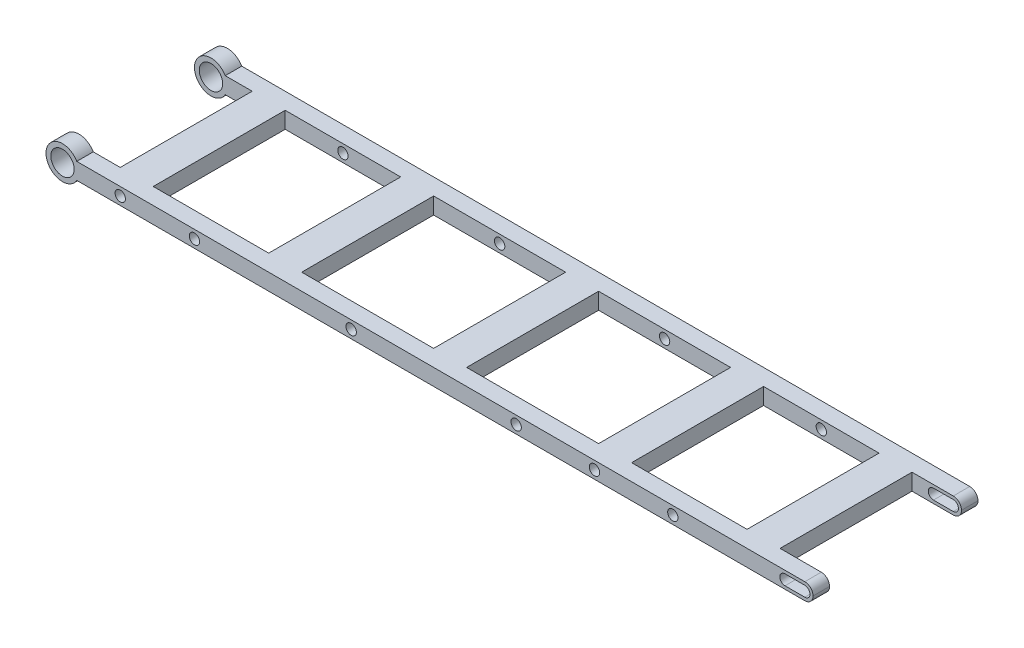
SolidWorks part; units mm, degrees
ref_plane "Front Plane" through (0, 0, 0) normal (0, 0, 1) x (1, 0, 0)
ref_plane "Top Plane" through (0, 0, 0) normal (0, 1, 0) x (1, 0, 0)
ref_plane "Right Plane" through (0, 0, 0) normal (1, 0, 0) x (0, 0, -1)
sketch "Sketch1" plane through (0, 0, 0) normal (0, 1, 0) x (1, 0, 0)
  line L0 (-146.05, 25.4) -> (-127, 25.4)
  line L1 (-146.05, 31.75) -> (146.05, 31.75)
  line L2 (-146.05, 31.75) -> (-146.05, 25.4)
  line L3 (-146.05, -31.75) -> (146.05, -31.75)
  line L4 (146.05, 31.75) -> (146.05, 25.4)
  line L5 (-146.05, 31.75) -> (146.05, -31.75) construction
  line L6 (-146.05, -31.75) -> (146.05, 31.75) construction
  line L8 (-146.05, -25.4) -> (-127, -25.4)
  line L10 (0, 31.75) -> (0, -31.75) construction
  line L11 (-6.35, 25.4) -> (-6.35, -25.4)
  line L12 (127, 25.4) -> (127, -25.4)
  line L14 (-6.35, 31.75) -> (-6.35, -31.75) construction
  line L15 (-57.15, 25.4) -> (-57.15, -25.4)
  line L20 (-69.85, 25.4) -> (-69.85, -25.4)
  line L21 (-114.3, 25.4) -> (-114.3, -25.4)
  line L22 (-127, 25.4) -> (-127, -25.4)
  line L23 (-146.05, -25.4) -> (-146.05, -31.75)
  line L24 (146.05, -25.4) -> (146.05, -31.75)
  line L32 (-114.3, 25.4) -> (-69.85, 25.4)
  line L33 (-114.3, -25.4) -> (-69.85, -25.4)
  line L36 (-57.15, -25.4) -> (-6.35, -25.4)
  line L38 (-57.15, 25.4) -> (-6.35, 25.4)
  line L47 (127, -25.4) -> (146.05, -25.4)
  line L48 (127, 25.4) -> (146.05, 25.4)
  line L50 (57.15, 25.4) -> (6.35, 25.4)
  line L51 (6.35, 25.4) -> (6.35, -25.4)
  line L52 (57.15, -25.4) -> (6.35, -25.4)
  line L53 (57.15, 25.4) -> (57.15, -25.4)
  line L54 (114.3, 25.4) -> (69.85, 25.4)
  line L55 (69.85, 25.4) -> (69.85, -25.4)
  line L56 (114.3, -25.4) -> (69.85, -25.4)
  line L57 (114.3, 25.4) -> (114.3, -25.4)
  point P0 (0, 0)
  dimension "D1" = 63.5
  dimension "D2" = 292.1
  dimension "D4" = 6.35
  dimension "D3" = 6.35
  dimension "D14" = 6.35
  dimension "D5" = 19.05
  dimension "D7" = 44.45
  dimension "D8" = 19.05
  dimension "D6" = 50.8
  dimension "D13" = 12.7
extrude "Boss-Extrude1" add sketch "Sketch1" against normal blind 6.35
fillet "Fillet2" radius 3.175 8 edges at (-146.05, -6.35, 28.575) (-146.05, 0, 28.575) (-146.05, -6.35, -28.575) (-146.05, 0, -28.575) (146.05, -6.35, -28.575) (146.05, 0, -28.575) (146.05, -6.35, 28.575) (146.05, 0, 28.575)
sketch "Sketch2" plane through (0, 0, 31.75) normal (0, 0, 1) x (1, 0, 0)
  line L0 (-142.875, 0) -> (-142.875, -6.35) construction
  line L1 (0, 0) -> (0, -6.35) construction
  line L2 (-114.3, 0) -> (-69.85, 0) construction
  line L3 (-114.3, 0) -> (-69.85, 0)
  line L4 (142.875, 0) -> (-142.875, 0)
  line L5 (-57.15, 0) -> (-6.35, 0) construction
  line L6 (-142.875, -6.35) -> (142.875, -6.35)
  line L7 (-57.15, 0) -> (-6.35, 0)
  line L8 (142.875, 0) -> (-142.875, 0)
  line L10 (-142.875, -6.35) -> (142.875, -6.35)
  line L16 (-31.75, 0) -> (-31.75, -6.35) construction
  line L17 (-92.075, 0) -> (-92.075, -6.35) construction
  line L19 (135.255, -1.1811) -> (142.875, -1.1811)
  line L20 (31.75, 0) -> (31.75, -6.35) construction
  line L21 (135.255, -5.1689) -> (142.875, -5.1689)
  line L22 (92.075, 0) -> (92.075, -6.35) construction
  line L23 (-127, 0) -> (-142.875, 0) construction
  line L24 (-127, 0) -> (-142.875, 0)
  line L25 (-127, 0) -> (-114.3, 0)
  line L26 (31.75, -3.175) -> (92.075, -3.175)
  circle A0 centre (-142.875, -3.175) radius 6.35
  circle A5 centre (-142.875, -3.175) radius 4.4996
  circle A6 centre (-92.075, -3.175) radius 1.9939
  circle A15 centre (-31.75, -3.175) radius 1.9939
  circle A16 centre (31.75, -3.175) radius 1.9939
  circle A17 centre (92.075, -3.175) radius 1.9939
  arc A19 (-142.875, 0) -> (-146.05, -3.175) centre (-142.875, -3.175) ccw
  arc A20 (-142.875, 0) -> (-146.05, -3.175) centre (-142.875, -3.175) ccw
  arc A21 (-146.05, -3.175) -> (-142.875, -6.35) centre (-142.875, -3.175) ccw
  arc A22 (-146.05, -3.175) -> (-142.875, -6.35) centre (-142.875, -3.175) ccw
  arc A23 (142.875, -6.35) -> (146.05, -3.175) centre (142.875, -3.175) ccw
  arc A24 (142.875, -6.35) -> (146.05, -3.175) centre (142.875, -3.175) ccw
  arc A25 (146.05, -3.175) -> (142.875, 0) centre (142.875, -3.175) ccw
  arc A26 (146.05, -3.175) -> (142.875, 0) centre (142.875, -3.175) ccw
  arc A27 (142.875, -5.1689) -> (142.875, -1.1811) centre (142.875, -3.175) ccw
  arc A28 (135.255, -1.1811) -> (135.255, -5.1689) centre (135.255, -3.175) ccw
  circle A29 centre (-120.65, -3.175) radius 1.9939
  circle A30 centre (61.9125, -3.175) radius 1.9939
  point P15 (-92.075, 0)
  point P46 (61.9125, -3.175)
  dimension "D1" = 12.7
  dimension "D4" = 3.9878
  dimension "D5" = 3.9878
  dimension "D6" = 31.75
  dimension "D7" = 92.075
  dimension "D11" = 8.9992
  dimension "D12" = 3.9878
  dimension "D13" = 3.9878
  dimension "D14" = 22.225
  dimension "D15" = 3.9878
  dimension "D3" = 3.9878
  dimension "D8" = 3.9878
  dimension "D10" = 7.62
  dimension "D9" = 3.9878
  dimension "D2" = 0
extrude "Boss-Extrude3" add sketch "Sketch2" along direction (0, 0, -1) on the side against the normal up to surface (6.35 mm away) contours A0 up to face at (-137.423, -3.175, 25.4)
sketch "Sketch4" plane through (0, 0, -31.75) normal (0, 0, -1) x (-1, 0, 0)
  circle A0 centre (142.875, -3.175) radius 6.35 construction
  circle A1 centre (142.875, -3.175) radius 6.35
extrude "Boss-Extrude4" add sketch "Sketch4" against normal up to surface (6.35 mm away) up to face at (-137.423, -3.175, -25.4)
extrude "Cut-Extrude1" cut sketch "Sketch2<4>" against normal up to surface (63.5 mm away) contours L19 A28 L21 A27 | A5 | A6 | A15 | A16 | A17 | A29 | A30 region at (139.065, -3.175, 31.75) up to face at (29.3029, -3.175, -31.75)
sketch "Sketch2<4>" plane through (0, 0, 31.75) normal (0, 0, 1) x (1, 0, 0) same geometry as "Sketch2"
